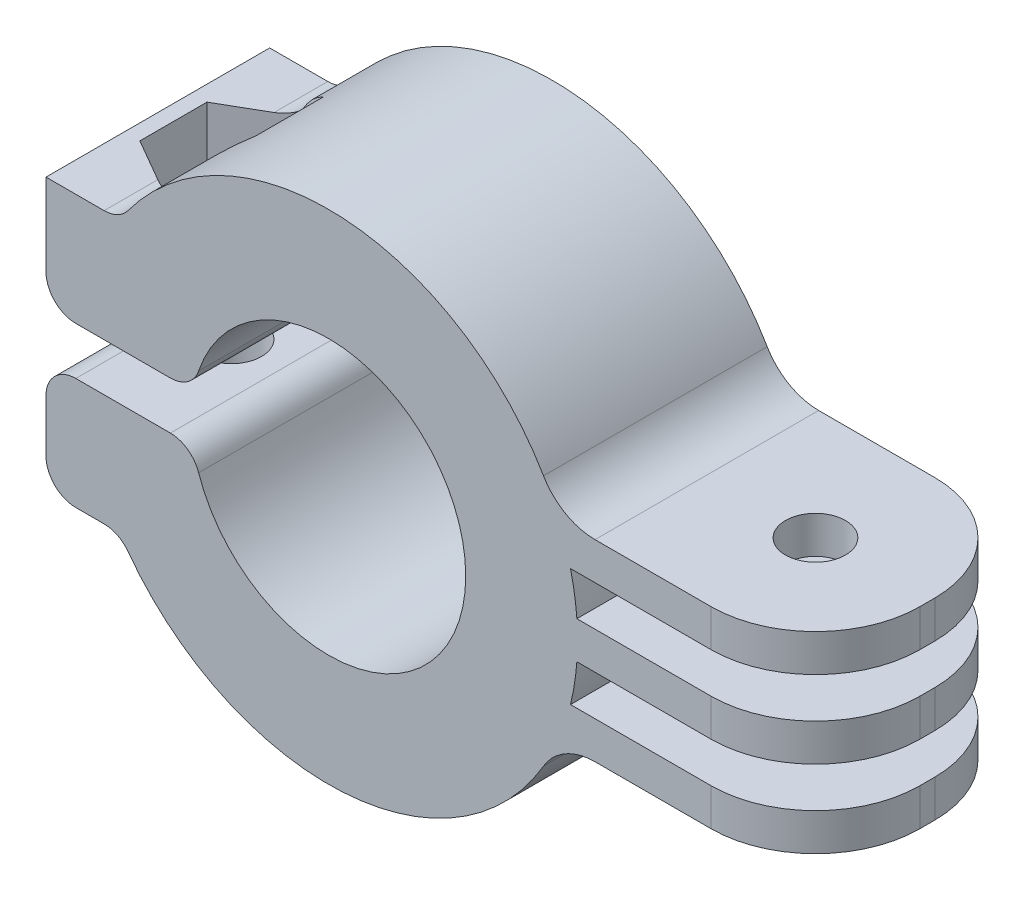
SolidWorks part; units mm, degrees
ref_plane "Front Plane" through (0, 0, 0) normal (0, 0, 1) x (1, 0, 0)
ref_plane "Top Plane" through (0, 0, 0) normal (0, 1, 0) x (1, 0, 0)
ref_plane "Right Plane" through (0, 0, 0) normal (1, 0, 0) x (0, 0, -1)
sketch "Sketch1" plane through (0, 0, 0) normal (0, 0, 1) x (1, 0, 0)
  line L0 (32.7383, 9.5052) -> (32.7383, -9.1865) construction
  line L1 (0, 0) -> (-11.5065, 2.0289) construction
  line L2 (0, 0) -> (-1531.3654, 0) construction
  line L3 (-11.5065, 2.0289) -> (-24.0648, 2.0289)
  line L4 (-24.0648, 2.0289) -> (-24.0648, 11.5539)
  line L5 (-24.0648, 11.5539) -> (-17.7856, 11.5539)
  line L6 (-15.4044, -11.5539) -> (-15.4044, -2.0289) construction
  line L7 (-20.1669, 11.5539) -> (-15.4044, 11.5539) construction
  line L8 (-20.1669, 11.5539) -> (-20.1669, 2.0289) construction
  line L9 (-20.1669, 2.0289) -> (-15.4044, 2.0289) construction
  line L10 (-15.4044, 11.5539) -> (-15.4044, 2.0289) construction
  line L11 (-20.1669, -2.0289) -> (-15.4044, -2.0289) construction
  line L12 (-20.1669, -11.5539) -> (-20.1669, -2.0289) construction
  line L13 (-20.1669, -11.5539) -> (-15.4044, -11.5539) construction
  line L14 (0, 0) -> (-11.5065, -2.0289) construction
  line L15 (-24.0648, -11.5539) -> (-17.7856, -11.5539)
  line L16 (-24.0648, -2.0289) -> (-24.0648, -11.5539)
  line L17 (-11.5065, -2.0289) -> (-24.0648, -2.0289)
  line L18 (41.4695, -1.5875) -> (21.1495, -1.5875)
  line L19 (41.4695, -1.5875) -> (41.4695, 1.5875)
  line L20 (41.4695, 1.5875) -> (21.1495, 1.5875)
  line L22 (37.5008, 9.5052) -> (37.5008, -9.1865) construction
  line L23 (32.7383, -9.1865) -> (37.5008, -9.1865) construction
  line L24 (32.7383, 9.5052) -> (37.5008, 9.5052) construction
  line L25 (20.6072, 5.0165) -> (41.4695, 5.0165)
  line L26 (41.4695, 5.0165) -> (41.4695, 8.1915)
  line L27 (41.4695, 8.1915) -> (19.5633, 8.1915)
  line L28 (28.7695, 9.5052) -> (41.4695, 9.5052) construction
  line L29 (41.4695, -8.1915) -> (19.5633, -8.1915)
  line L30 (41.4695, -5.0165) -> (41.4695, -8.1915)
  line L31 (20.6072, -5.0165) -> (41.4695, -5.0165)
  line L32 (28.7695, 9.5052) -> (28.7695, -9.1865) construction
  line L33 (28.7695, -9.1865) -> (41.4695, -9.1865) construction
  line L34 (41.4695, -9.1865) -> (41.4695, 9.5052) construction
  arc A0 (-11.5065, 2.0289) -> (0, 11.684) centre (0, 0) cw
  arc A1 (-17.7856, 11.5539) -> (-17.7856, -11.5539) centre (0, 0) cw
  arc A2 (-20.8868, 3.6829) -> (0, 21.209) centre (0, 0) cw construction
  arc A3 (-11.5065, -2.0289) -> (0, 11.684) centre (0, 0) ccw
  point P13 (-17.7856, 2.0289)
  point P14 (41.4695, 0)
  point P17 (-17.7856, 2.0289)
  point P24 (-17.7856, 11.5539)
  point P42 (35.1195, 9.5052)
  dimension "D2" = 11.684
  dimension "D4" = 9.525
  dimension "D5" = 4.7625
  dimension "D1" = 10
  dimension "D6" = 3.175
  dimension "D7" = 4.7625
  dimension "D8" = 3.429
  dimension "D9" = 20.32
  dimension "D10" = 12.7
  dimension "D3" = 9.525
extrude "Body" add sketch "Sketch1" along normal blind 19.05 contours A3 L17 L16 L15 A1 L5 L4 L3 A0 | L31 A1 L29 L30 | L20 A1 L18 L19 | L27 A1 L25 L26 region at (-17.7856, 2.6493, 0) region at (30.7984, 6.6169, 0) region at (31.3293, 0, 0) region at (30.7984, -6.6169, 0)
hole_wizard "CBORE for #10 Binding Head Machine Screw1" positions "Sketch2" profile "Sketch3" counterbore size "#10" standard "ANSI Inch" end condition through all
sketch "Sketch2" plane through (0, -11.5539, 0) normal (0, -1, 0) x (-1, 0, 0)
  line L0 (17.7856, -19.05) -> (17.7856, 0) construction
  point P0 (17.7856, -9.525)
sketch "Sketch3" plane through (-17.7856, -11.5539, 9.525) normal (1, 0, 0) x (0, 0, -1)
  line L0 (0, 0) -> (0, 32.7629)
  line L1 (0, 32.7629) -> (2.5527, 32.7629)
  line L3 (2.5527, 32.7629) -> (2.5527, 3.1242)
  line L4 (2.5527, 3.1242) -> (5.9436, 3.1242)
  line L5 (5.9436, 3.1242) -> (5.9436, 0)
  line L7 (5.9436, 0) -> (0, 0)
  line L11 (0, -6.35) -> (0, 107.95) construction
  dimension "Thru Hole Dia." = 5.1054
  dimension "Thru Hole Depth" = 32.7629
  dimension "C'Bore Dia." = 11.8872
  dimension "C'Bore Depth" = 3.1242
sketch "Sketch4" plane through (0, -8.4297, 0) normal (0, -1, 0) x (1, 0, 0)
  circle A1 centre (-17.7856, 9.525) radius 5.9436
  circle A2 centre (-17.7856, 9.525) radius 5.9436
  dimension "D1" = 0
extrude "#10 Head clearance" cut sketch "Sketch4" along normal through all
sketch "Sketch5" plane through (0, 11.5539, 0) normal (0, 1, 0) x (1, 0, 0)
  line L1 (-22.7386, -6.6654) -> (-22.7386, -12.3846)
  line L2 (-22.7386, -12.3846) -> (-17.7856, -15.2442)
  line L3 (-17.7856, -15.2442) -> (-12.8326, -12.3846)
  line L4 (-12.8326, -12.3846) -> (-12.8326, -6.6654)
  line L5 (-12.8326, -6.6654) -> (-17.7856, -3.8058)
  line L6 (-17.7856, -3.8058) -> (-22.7386, -6.6654)
  arc A0 (-17.7856, -6.9723) -> (-17.7856, -12.0777) centre (-17.7856, -9.525) ccw construction
  arc A1 (-17.7856, -6.9723) -> (-17.7856, -12.0777) centre (-17.7856, -9.525) ccw construction
  circle A2 centre (-17.7856, -9.525) radius 4.953 construction
  line M7 (-17.7856, -19.05) -> (-17.7856, -12.0777)
  arc M8 (-17.7856, -12.0777) -> (-17.7856, -6.9723) centre (-17.7856, -9.525) cw
  line M9 (-17.7856, -6.9723) -> (-17.7856, 0)
  dimension "D1" = 9.906
extrude "#10 nut clearance" cut sketch "Sketch5" along direction (0, 1, 0) on the side against the normal blind 4.7625 and the other way through all contours L6 L1 L2 M9 M7 M8 | L4 L5 L3 M9 M8 M7 region at (-20.3417, 11.5539, 9.525) region at (-16.222, 11.5539, 9.525)
fillet "Fillet2" radius 8.89 6 edges at (41.4695, -6.604, 0) (41.4695, 0, 0) (41.4695, 6.604, 0) (41.4695, 6.604, 19.05) (41.4695, 0, 19.05) (41.4695, -6.604, 19.05)
hole_wizard "#10 Clearance Hole1" positions "Sketch7" profile "Sketch8" hole size "#10" standard "ANSI Inch" end condition through all
sketch "Sketch7" plane through (0, -8.1915, 0) normal (0, -1, 0) x (-1, 0, 0)
  line L0 (-41.4695, -9.525) -> (-19.5633, -9.525) construction
  line L1 (-41.4695, -10.16) -> (-41.4695, -8.89) construction
  line L2 (-19.5633, -19.05) -> (-19.5633, 0) construction
  circle A0 centre (-31.9445, -9.525) radius 9.525 construction
  point P9 (-31.9445, -9.525)
  dimension "D1" = 19.05
sketch "Sketch8" plane through (31.9445, -8.1915, 9.525) normal (1, 0, 0) x (0, 0, -1)
  line L0 (0, 0) -> (0, 29.4005)
  line L1 (0, 29.4005) -> (2.5527, 29.4005)
  line L2 (2.5527, 29.4005) -> (2.5527, 0)
  line L5 (2.5527, 0) -> (0, 0)
  line L11 (0, -6.35) -> (0, 107.95) construction
  dimension "Thru Hole Dia." = 5.1054
  dimension "Thru Hole Depth" = 29.4005
fillet "Fillet3" radius 5.08 2 edges at (19.5633, 8.1915, 9.525) (19.5633, -8.1915, 9.525)
fillet "Fillet4" radius 2.54 9 edges at (-17.7856, 11.5539, 1.9029) (-17.7856, 11.5539, 17.1471) (-17.7856, -11.5539, 1.7907) (-17.7856, -11.5539, 17.2593) (-24.0648, -11.5539, 9.525) (-24.0648, -2.0289, 9.525) (-24.0648, 2.0289, 9.525) (-11.5065, -2.0289, 9.525) (-11.5065, 2.0289, 9.525)
equation "\"D2@Sketch1\"= \"yagi_diam\" / 2 + \"tol\""
equation "\"yagi_diam\"= 0.88"
equation "\"tol\"= 0.02"
equation "\"D1@Sketch5\"=0.37+\"tol\""
equation "\"D8@Sketch1\"=0.125+0.010"
